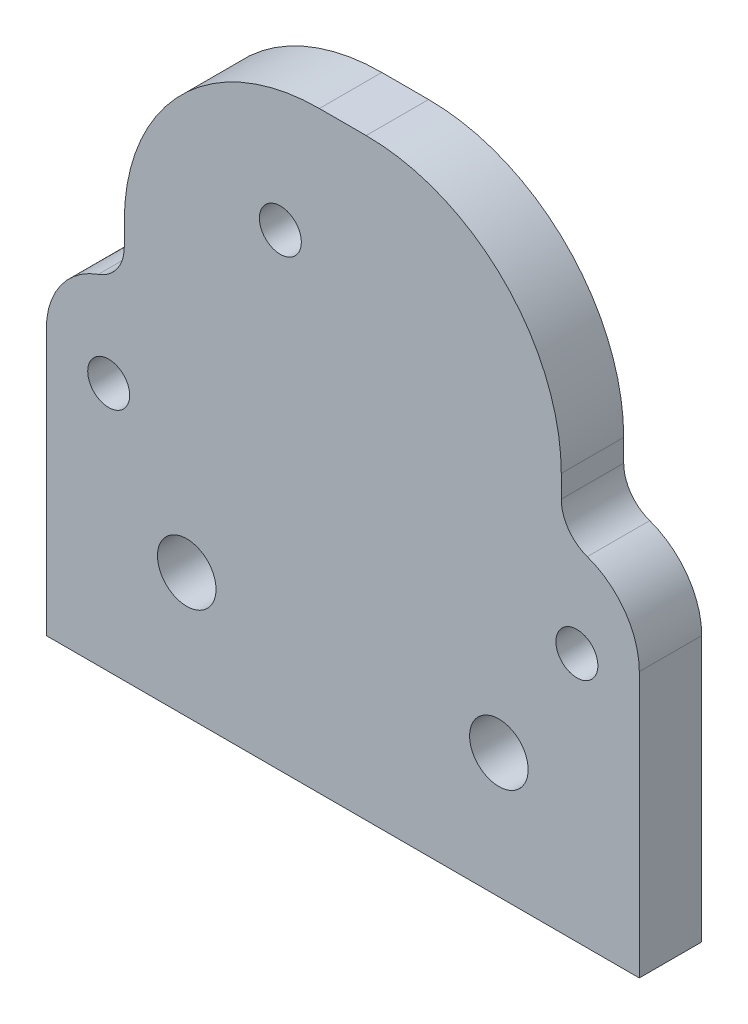
SolidWorks part; units mm, degrees
ref_plane "Front Plane" through (0, 0, 0) normal (0, 0, 1) x (1, 0, 0)
ref_plane "Top Plane" through (0, 0, 0) normal (0, 1, 0) x (1, 0, 0)
ref_plane "Right Plane" through (0, 0, 0) normal (1, 0, 0) x (0, 0, -1)
sketch "Sketch1" plane through (0, 0, 0) normal (0, 1, 0) x (1, 0, 0)
  line L1 (0, 0) -> (30.4, 0)
  line L2 (0, 0) -> (0, -3.2)
  line L3 (0, -3.2) -> (30.4, -3.2)
  line L4 (30.4, 0) -> (30.4, -3.2)
  dimension "D1" = 3.2
  dimension "D2" = 30.4
extrude "Boss-Extrude1" add sketch "Sketch1" along normal blind 17.6
sketch "Sketch2" plane through (0, 0, 3.2) normal (0, 0, 1) x (1, 0, 0)
  line L0 (30.4, 17.6) -> (30.4, 0) construction
  line L1 (0, 0) -> (30.4, 0) construction
  circle A0 centre (23.2, 6.4) radius 1.5
  circle A1 centre (7.2, 6.4) radius 1.5
  dimension "D5" = 3
  dimension "D6" = 3
  dimension "D1" = 7.2
  dimension "D2" = 6.4
  dimension "D3" = 6.4
  dimension "D4" = 16
extrude "Cut-Extrude1" cut sketch "Sketch2" against normal blind 16
sketch "Sketch3" plane through (0, 0, 0) normal (0, 0, -1) x (-1, 0, 0)
  line L0 (0, 17.6) -> (0, 0) construction
  line L1 (-30.4, 17.6) -> (0, 17.6) construction
  circle A0 centre (-27.2, 12.8) radius 1.075
  circle A1 centre (-3.2, 12.8) radius 1.075
  dimension "D2" = 2.15
  dimension "D3" = 2.15
  dimension "D1" = 24
  dimension "D4" = 3.2
  dimension "D5" = 4.8
  dimension "D6" = 4.8
extrude "Cut-Extrude2" cut sketch "Sketch3" against normal blind 16
sketch "Sketch4" plane through (0, 17.6, 0) normal (0, 1, 0) x (1, 0, 0)
  line L0 (0, -3.2) -> (30.4, -3.2) construction
  line L1 (4, -3.2) -> (26.4, -3.2)
  line L2 (4, -3.2) -> (4, 0)
  line L3 (4, 0) -> (26.4, 0)
  line L4 (26.4, -3.2) -> (26.4, 0)
  line L5 (30.4, 0) -> (0, 0) construction
  dimension "D1" = 4
  dimension "D2" = 4
extrude "Boss-Extrude2" add sketch "Sketch4" along normal blind 12.8
sketch "Sketch5" plane through (0, 0, 3.2) normal (0, 0, 1) x (1, 0, 0)
  line L1 (4, 30.4) -> (26.4, 30.4) construction
  line L2 (4, 30.4) -> (4, 17.6) construction
  circle A0 centre (12, 24) radius 1.075
  dimension "D2" = 6.4
  dimension "D1" = 2.15
  dimension "D3" = 8
extrude "Cut-Extrude3" cut sketch "Sketch5" against normal blind 16
fillet "Fillet1" radius 10 2 edges at (4, 30.4, 1.6) (26.4, 30.4, 1.6)
fillet "Fillet2" radius 4 2 edges at (30.4, 17.6, 1.6) (0, 17.6, 1.6)
fillet "Fillet3" radius 2 2 edges at (26.4, 17.6, 1.6) (4, 17.6, 1.6)
equation "\"滑动-垂直孔\" = 0.6"
equation "\"滑动-水平孔\" = 0.3"
equation "\"松动-垂直孔\" = 0.3"
equation "\"松动-水平孔\" = 0.1"
equation "\"正常-垂直孔\" = 0.15"
equation "\"正常-水平孔\" = 0"
equation "\"紧缩-垂直孔\" = 0"
equation "\"紧缩-水平孔\" = -0.1"
equation "\"_喷嘴物理宽度\" = 0.8"
equation "\"_喷嘴宽度系数\" = 1"
equation "\"_物理厚度\" = 0.4"
equation "\"_物理厚度系数\" = 2"
equation "\"喷嘴宽度\" = \"_喷嘴物理宽度\" * \"_喷嘴宽度系数\""
equation "\"喷嘴厚度\" = \"_物理厚度\" * \"_物理厚度系数\""
equation "\"D1@Sketch1\"=\"喷嘴宽度\"*4"
equation "\"D2@Sketch1\"=\"喷嘴宽度\"*38"
equation "\"D1@Boss-Extrude1\"=\"喷嘴宽度\"*22"
equation "\"D1@Sketch2\"=\"喷嘴宽度\"*9"
equation "\"D2@Sketch2\"=\"喷嘴宽度\"*8"
equation "\"D3@Sketch2\"=\"D2@Sketch2\""
equation "\"D4@Sketch2\"=\"喷嘴厚度\"*20"
equation "\"D5@Sketch2\"=\"紧缩-垂直孔\"+3"
equation "\"D6@Sketch2\"=\"D5@Sketch2\""
equation "\"D2@Sketch3\"=\"正常-垂直孔\"+2"
equation "\"D3@Sketch3\"=\"D2@Sketch3\""
equation "\"D4@Sketch3\"=\"喷嘴宽度\"*4"
equation "\"D5@Sketch3\"=\"喷嘴宽度\"*6"
equation "\"D6@Sketch3\"=\"D5@Sketch3\""
equation "\"D1@Sketch4\"=\"喷嘴宽度\"*5"
equation "\"D2@Sketch4\"=\"D1@Sketch4\""
equation "\"D1@Boss-Extrude2\"=\"喷嘴宽度\"*16"
equation "\"D1@Sketch5\"=\"正常-垂直孔\"+2"
equation "\"D2@Sketch5\"=\"喷嘴宽度\"*8"
equation "\"D3@Sketch5\"=\"喷嘴宽度\"*10"
